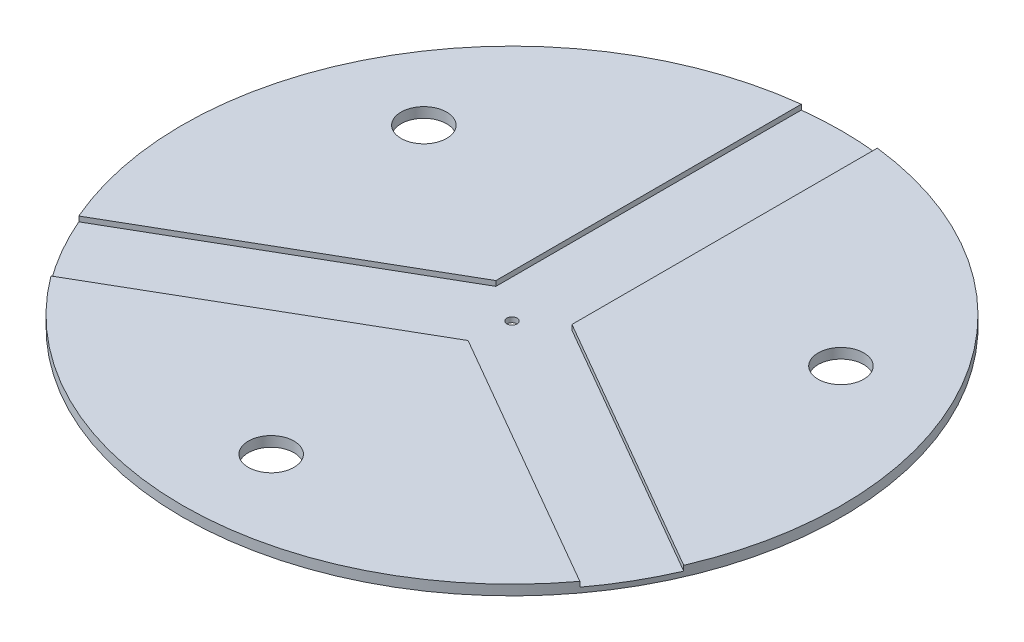
SolidWorks part; units mm, degrees
ref_plane "Front Plane" through (0, 0, 0) normal (0, 0, 1) x (1, 0, 0)
ref_plane "Top Plane" through (0, 0, 0) normal (0, 1, 0) x (1, 0, 0)
ref_plane "Right Plane" through (0, 0, 0) normal (1, 0, 0) x (0, 0, -1)
sketch "Sketch1" plane through (0, 0, 0) normal (0, 1, 0) x (1, 0, 0)
  circle A0 centre (0, 0) radius 65
  circle A1 centre (0, 0) radius 1
  dimension "D1" = 130
  dimension "D2" = 2
extrude "Boss-Extrude1" add sketch "Sketch1" along normal mid plane 2
sketch "Sketch2" plane through (0, 1, 0) normal (0, 1, 0) x (1, 0, 0)
  line L0 (0, 65) -> (0, 36.8262) construction
  line L3 (67.5348, -30.331) -> (7.5, 4.3301)
  line L4 (-7.5, 73.6523) -> (7.5, 73.6523)
  line L5 (-7.5, 73.6523) -> (-7.5, 4.3301)
  line L7 (7.5, 73.6523) -> (7.5, 4.3301)
  line L8 (-7.5, 73.6523) -> (6.5006, 4.9071) construction
  line L9 (0, 36.8262) -> (7.5, 73.6523) construction
  line L10 (67.5348, -30.331) -> (60.0348, -43.3214)
  line L11 (60.0348, -43.3214) -> (0, -8.6603)
  line L13 (-60.0348, -43.3214) -> (0, -8.6603)
  line L14 (-60.0348, -43.3214) -> (-67.5348, -30.331)
  line L15 (-67.5348, -30.331) -> (-7.5, 4.3301)
  circle A0 centre (0, 0) radius 65 construction
  point P1 (0, 36.8262)
  point P23 (0, 0)
  dimension "D3" = 3
extrude "Cut-Extrude1" cut sketch "Sketch2" against normal blind 1
sketch "Sketch3" plane through (0, 0, 0) normal (0, 1, 0) x (1, 0, 0)
  line L0 (0, 1) -> (0, 38.2598) construction
  line L1 (0, 0) -> (41.1362, 23.75) construction
  circle A0 centre (41.1362, 23.75) radius 4.5
  circle A1 centre (0, 0) radius 1 construction
  circle A2 centre (0, -47.5) radius 4.5
  circle A3 centre (-41.1362, 23.75) radius 4.5
  point P15 (0, 0)
  dimension "D2" = 9
  dimension "D1" = 47.5
  dimension "D3" = 60
  dimension "D4" = 3
extrude "Cut-Extrude2" cut sketch "Sketch3" against normal through all and the other way blind 1
